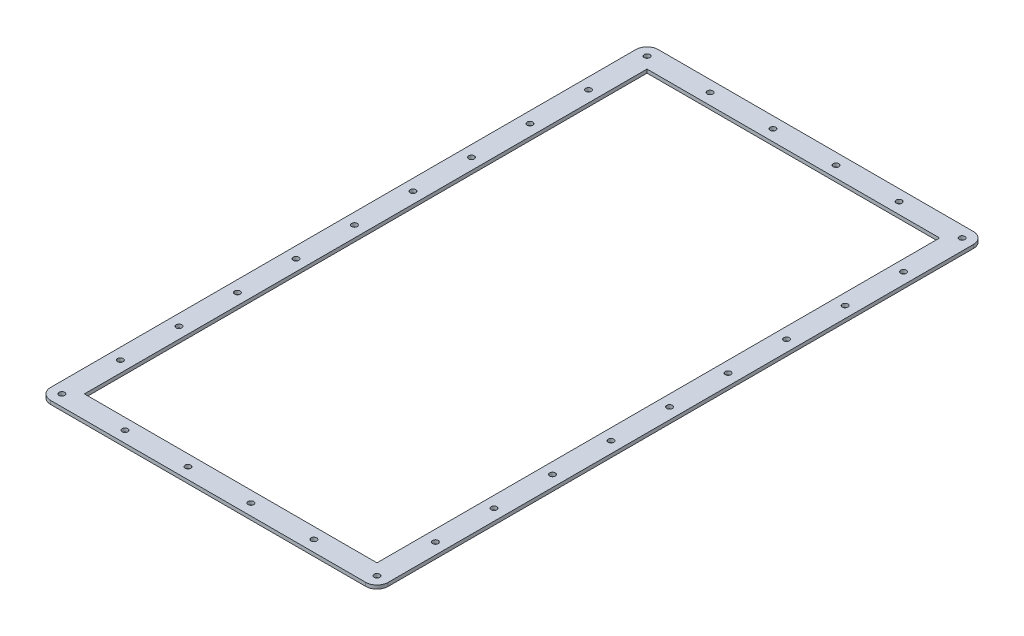
SolidWorks part; units mm, degrees
material "5052-H32"
ref_plane "Front Plane" through (0, 0, 0) normal (0, 0, 1) x (1, 0, 0)
ref_plane "Top Plane" through (0, 0, 0) normal (0, 1, 0) x (1, 0, 0)
ref_plane "Right Plane" through (0, 0, 0) normal (1, 0, 0) x (0, 0, -1)
sketch "Sketch1" plane through (0, 0, 0) normal (0, 1, 0) x (1, 0, 0)
  line L0 (-150, 270) -> (150, 270)
  line L1 (-130, -250) -> (130, -250)
  line L2 (-130, -250) -> (-130, 250)
  line L3 (-130, 250) -> (130, 250)
  line L4 (130, -250) -> (130, 250)
  line L5 (-130, -250) -> (130, 250) construction
  line L6 (-130, 250) -> (130, -250) construction
  line L7 (150, -270) -> (150, 270)
  line L8 (-150, -270) -> (150, -270)
  line L9 (-150, -270) -> (-150, 270)
  line L12 (130, 0) -> (-130, 0) construction
  circle A34 centre (140, 260) radius 2.5
  circle A35 centre (84, 260) radius 2.5
  circle A36 centre (28, 260) radius 2.5
  circle A37 centre (-28, 260) radius 2.5
  circle A38 centre (-84, 260) radius 2.5
  circle A39 centre (-140, 260) radius 2.5
  circle A44 centre (-140, 208) radius 2.5
  circle A49 centre (-140, 156) radius 2.5
  circle A54 centre (-140, 104) radius 2.5
  circle A59 centre (-140, 52) radius 2.5
  circle A64 centre (-140, 0) radius 2.5
  circle A69 centre (-140, -52) radius 2.5
  circle A74 centre (-140, -104) radius 2.5
  circle A79 centre (-140, -156) radius 2.5
  circle A84 centre (-140, -208) radius 2.5
  circle A85 centre (84, -260) radius 2.5
  circle A86 centre (28, -260) radius 2.5
  circle A87 centre (-28, -260) radius 2.5
  circle A88 centre (-84, -260) radius 2.5
  circle A89 centre (-140, -260) radius 2.5
  circle A90 centre (140, 208) radius 2.5
  circle A91 centre (140, 156) radius 2.5
  circle A92 centre (140, 104) radius 2.5
  circle A93 centre (140, 52) radius 2.5
  circle A94 centre (140, 0) radius 2.5
  circle A95 centre (140, -52) radius 2.5
  circle A96 centre (140, -104) radius 2.5
  circle A97 centre (140, -156) radius 2.5
  circle A98 centre (140, -208) radius 2.5
  circle A99 centre (140, -260) radius 2.5
  circle A100 centre (84, 208) radius 2.5 [skipped]
  circle A101 centre (28, 208) radius 2.5 [skipped]
  circle A102 centre (-28, 208) radius 2.5 [skipped]
  circle A103 centre (-84, 208) radius 2.5 [skipped]
  circle A104 centre (84, 156) radius 2.5 [skipped]
  circle A105 centre (28, 156) radius 2.5 [skipped]
  circle A106 centre (-28, 156) radius 2.5 [skipped]
  circle A107 centre (-84, 156) radius 2.5 [skipped]
  circle A108 centre (84, 104) radius 2.5 [skipped]
  circle A109 centre (28, 104) radius 2.5 [skipped]
  circle A110 centre (-28, 104) radius 2.5 [skipped]
  circle A111 centre (-84, 104) radius 2.5 [skipped]
  circle A112 centre (84, 52) radius 2.5 [skipped]
  circle A113 centre (28, 52) radius 2.5 [skipped]
  circle A114 centre (-28, 52) radius 2.5 [skipped]
  circle A115 centre (-84, 52) radius 2.5 [skipped]
  circle A116 centre (84, 0) radius 2.5 [skipped]
  circle A117 centre (28, 0) radius 2.5 [skipped]
  circle A118 centre (-28, 0) radius 2.5 [skipped]
  circle A119 centre (-84, 0) radius 2.5 [skipped]
  circle A120 centre (84, -52) radius 2.5 [skipped]
  circle A121 centre (28, -52) radius 2.5 [skipped]
  circle A122 centre (-28, -52) radius 2.5 [skipped]
  circle A123 centre (-84, -52) radius 2.5 [skipped]
  circle A124 centre (84, -104) radius 2.5 [skipped]
  circle A125 centre (28, -104) radius 2.5 [skipped]
  circle A126 centre (-28, -104) radius 2.5 [skipped]
  circle A127 centre (-84, -104) radius 2.5 [skipped]
  circle A128 centre (84, -156) radius 2.5 [skipped]
  circle A129 centre (28, -156) radius 2.5 [skipped]
  circle A130 centre (-28, -156) radius 2.5 [skipped]
  circle A131 centre (-84, -156) radius 2.5 [skipped]
  circle A132 centre (84, -208) radius 2.5 [skipped]
  circle A133 centre (28, -208) radius 2.5 [skipped]
  circle A134 centre (-28, -208) radius 2.5 [skipped]
  circle A135 centre (-84, -208) radius 2.5 [skipped]
  dimension "D4" = 5
  dimension "D2" = 500
  dimension "D1" = 20
  dimension "D3" = 260
  dimension "D5" = 10
  dimension "D6" = 10
  dimension "D9" = 52
  dimension "D10" = 56
  dimension "D7" = 6
  dimension "D8" = 11
extrude "Boss-Extrude1" add sketch "Sketch1" along normal blind 3.175 contours L9 L8 L7 L0 L4 L1 L2 L3 A34 region at (0, 0, -263.8226)
fillet "Fillet1" radius 10 4 edges at (150, 1.5875, 270) (-150, 1.5875, 270) (150, 1.5875, -270) (-150, 1.5875, -270)
equation "\"L\"= 500"
equation "\"W\"= 260"
equation "\"H\"= 110"
equation "\"Compartment Width\"= 90"
equation "\"T\"= 4.7625 * 2 / 3"
equation "\"Inside Fillet Radius\"= 10"
equation "\"Hole\"=15"
equation "\"D2@Sketch1\"=\"L\""
equation "\"D1@Boss-Extrude1\"=\"T\""
equation "\"D3@Sketch1\"=\"W\""
equation "\"D9@Sketch1\"=(\"L\"+20)/10"
equation "\"D10@Sketch1\"=(\"W\"+20)/5"
